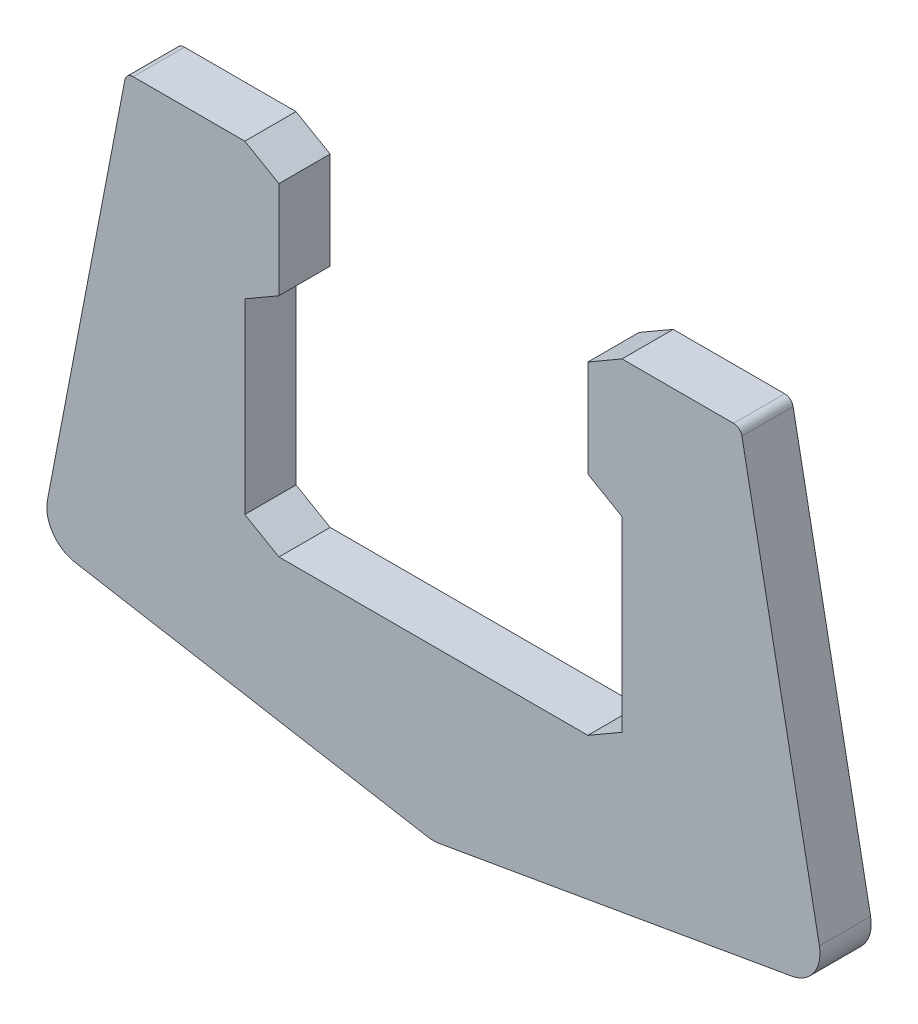
SolidWorks part; units mm, degrees
ref_plane "前视基准面" through (0, 0, 0) normal (0, 0, 1) x (1, 0, 0)
ref_plane "上视基准面" through (0, 0, 0) normal (0, 1, 0) x (1, 0, 0)
ref_plane "右视基准面" through (0, 0, 0) normal (1, 0, 0) x (0, 0, -1)
sketch "草图1" plane through (0, 0, 0) normal (0, 0, 1) x (1, 0, 0)
  line L0 (0, 6.5533) -> (0, -4.5416) construction
  line L1 (0, -30) -> (-23, -26)
  line L2 (-23, -26) -> (-18, 0)
  line L3 (-18, 0) -> (-11.05, 0)
  line L4 (-11.05, 0) -> (-9.05, -1.1547)
  line L5 (-9.05, -1.1547) -> (-9.05, -6.8453)
  line L6 (-9.05, -6.8453) -> (-11.05, -8)
  line L7 (-11.05, -8) -> (-11.05, -18.9453)
  line L8 (-11.05, -18.9453) -> (-9.05, -20.1)
  line L9 (-9.05, -20.1) -> (9.05, -20.1)
  line L10 (11.05, -18.9453) -> (9.05, -20.1)
  line L11 (11.05, -8) -> (11.05, -18.9453)
  line L12 (9.05, -6.8453) -> (11.05, -8)
  line L13 (9.05, -1.1547) -> (9.05, -6.8453)
  line L14 (11.05, 0) -> (9.05, -1.1547)
  line L15 (18, 0) -> (11.05, 0)
  line L16 (23, -26) -> (18, 0)
  line L17 (0, -30) -> (23, -26)
  point P14 (0, -20.1)
  point P21 (0, 0)
  point P22 (23, -24.3274)
  point P23 (0, 0)
  point P24 (-5.8837, -20)
  point P25 (9.05, -1.1547)
  dimension "D1" = 36
  dimension "D2" = 30
  dimension "D3" = 60
  dimension "D4" = 60
  dimension "D5" = 20.1
  dimension "D6" = 8
  dimension "D7" = 46
  dimension "D8" = 4
  dimension "D9" = 18.1
  dimension "D10" = 22.1
extrude "凸台-拉伸1" add sketch "草图1" along normal mid plane 3
fillet "圆角1" radius 2 3 edges at (23, -26, 0) (0, -30, 0) (-23, -26, 0)
fillet "圆角2" radius 0.5 2 edges at (-18, 0, 0) (18, 0, 0)
